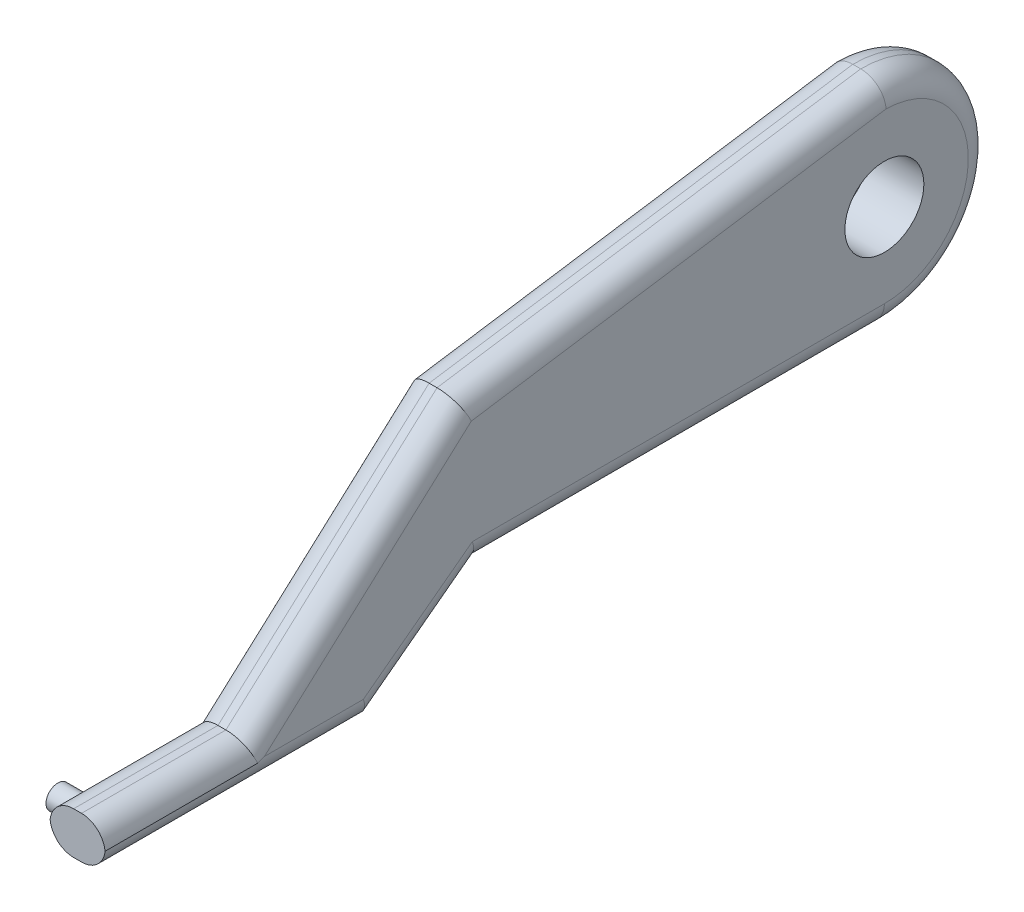
SolidWorks part; units mm, degrees
ref_plane "Front Plane" through (0, 0, 0) normal (0, 0, 1) x (1, 0, 0)
ref_plane "Top Plane" through (0, 0, 0) normal (0, 1, 0) x (1, 0, 0)
ref_plane "Right Plane" through (0, 0, 0) normal (1, 0, 0) x (0, 0, -1)
sketch "Sketch1" plane through (0, 0, 0) normal (1, 0, 0) x (0, 0, -1)
  line L0 (425.1779, 188.2855) -> (-111.3188, 106.7932)
  line L1 (-111.3188, 106.7932) -> (-378.6599, -134.8203)
  line L2 (425.1779, -84.3419) -> (-86.5568, -84.3419)
  line L3 (-86.5568, -84.3419) -> (-224.592, -188.2855)
  line L4 (-224.592, -188.2855) -> (-561.4916, -188.2855)
  line L5 (-378.6599, -134.8203) -> (-561.4916, -134.8203)
  line L6 (-561.4916, -134.8203) -> (-561.4916, -188.2855)
  circle A0 centre (425.1779, 51.9718) radius 50
  circle A1 centre (425.1779, 51.9718) radius 136.3137
extrude "Boss-Extrude4" add sketch "Sketch1" along normal blind 70 contours A1 L0 L1 L5 L6 L4 L3 L2 | L0 A1 A0
sketch "Sketch6" plane through (0, 0, 0) normal (-1, 0, 0) x (0, 0, 1)
  line L0 (561.4916, -134.8203) -> (561.4916, -188.2855) construction
  circle A0 centre (531.4916, -161.5529) radius 15
  dimension "D1" = 30
  dimension "D2" = 30
extrude "Boss-Extrude5" add sketch "Sketch6" along normal blind 20
fillet "Fillet5" radius 30 14 edges at (70, 51.9718, -561.4916) (0, 51.9718, -561.4916) (70, -136.3137, 155.5744) (70, -84.3419, -169.3105) (0, -84.3419, -169.3105) (70, 147.5393, -156.9295) (0, 147.5393, -156.9295) (70, -188.2855, 393.0418) (70, -134.8203, 470.0757) (0, -134.8203, 470.0757) (0, -188.2855, 393.0418) (0, -136.3137, 155.5744) (70, -14.0135, 244.9894) (0, -14.0135, 244.9894)
